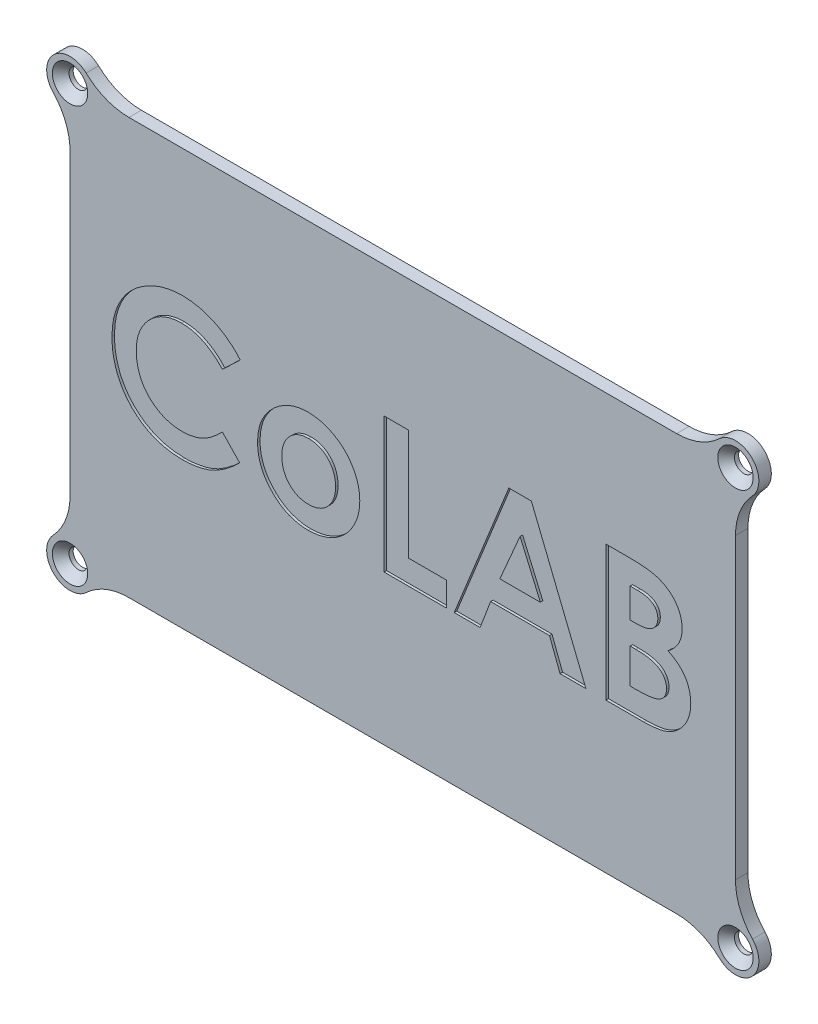
SolidWorks part; units mm, degrees
ref_plane "Front" through (0, 0, 0) normal (0, 0, 1) x (1, 0, 0)
ref_plane "Top" through (0, 0, 0) normal (0, 1, 0) x (1, 0, 0)
ref_plane "Right" through (0, 0, 0) normal (1, 0, 0) x (0, 0, -1)
sketch "Sketch2" plane through (0, 0, 0) normal (0, 0, 1) x (1, 0, 0)
  line L8 (80, -35.8441) -> (80, 35.8441)
  line L9 (65.8441, 50) -> (-65.8441, 50)
  line L10 (-80, 35.8441) -> (-80, -35.8441)
  line L11 (-65.8441, -50) -> (65.8441, -50)
  line L12 (80, -35.8441) -> (80, 35.8441)
  line L13 (65.8441, 50) -> (-65.8441, 50)
  line L14 (-80, 35.8441) -> (-80, -35.8441)
  line L15 (-65.8441, -50) -> (65.8441, -50)
  line L36 (76, -44) -> (76, 44)
  line L37 (-74, -46) -> (74, -46)
  line L38 (-76, 44) -> (-76, -44)
  line L39 (74, 46) -> (-74, 46)
  line L40 (76, -44) -> (76, 44)
  line L41 (-74, -46) -> (74, -46)
  line L42 (-76, 44) -> (-76, -44)
  line L43 (74, 46) -> (-74, 46)
  line L44 (73, 43) -> (-73, 43)
  line L45 (-73, 43) -> (-73, -43)
  line L46 (-73, -43) -> (73, -43)
  line L47 (73, -43) -> (73, 43)
  arc A12 (76.1393, -54.0909) -> (84.0909, -46.1393) centre (80, -50) ccw
  arc A13 (80, -35.8441) -> (84.0909, -46.1393) centre (95, -35.8441) ccw
  arc A14 (84.0909, 46.1393) -> (80, 35.8441) centre (95, 35.8441) ccw
  arc A15 (84.0909, 46.1393) -> (76.1393, 54.0909) centre (80, 50) ccw
  arc A16 (65.8441, 50) -> (76.1393, 54.0909) centre (65.8441, 65) ccw
  arc A17 (-76.1393, 54.0909) -> (-65.8441, 50) centre (-65.8441, 65) ccw
  arc A18 (-76.1393, 54.0909) -> (-84.0909, 46.1393) centre (-80, 50) ccw
  arc A19 (-80, 35.8441) -> (-84.0909, 46.1393) centre (-95, 35.8441) ccw
  arc A20 (-84.0909, -46.1393) -> (-80, -35.8441) centre (-95, -35.8441) ccw
  arc A21 (-84.0909, -46.1393) -> (-76.1393, -54.0909) centre (-80, -50) ccw
  arc A22 (-65.8441, -50) -> (-76.1393, -54.0909) centre (-65.8441, -65) ccw
  arc A23 (76.1393, -54.0909) -> (65.8441, -50) centre (65.8441, -65) ccw
  arc A24 (76.1393, -54.0909) -> (84.0909, -46.1393) centre (80, -50) ccw
  arc A25 (80, -35.8441) -> (84.0909, -46.1393) centre (95, -35.8441) ccw
  arc A26 (84.0909, 46.1393) -> (80, 35.8441) centre (95, 35.8441) ccw
  arc A27 (84.0909, 46.1393) -> (76.1393, 54.0909) centre (80, 50) ccw
  arc A28 (65.8441, 50) -> (76.1393, 54.0909) centre (65.8441, 65) ccw
  arc A29 (-76.1393, 54.0909) -> (-65.8441, 50) centre (-65.8441, 65) ccw
  arc A30 (-76.1393, 54.0909) -> (-84.0909, 46.1393) centre (-80, 50) ccw
  arc A31 (-80, 35.8441) -> (-84.0909, 46.1393) centre (-95, 35.8441) ccw
  arc A32 (-84.0909, -46.1393) -> (-80, -35.8441) centre (-95, -35.8441) ccw
  arc A33 (-84.0909, -46.1393) -> (-76.1393, -54.0909) centre (-80, -50) ccw
  arc A34 (-65.8441, -50) -> (-76.1393, -54.0909) centre (-65.8441, -65) ccw
  arc A35 (76.1393, -54.0909) -> (65.8441, -50) centre (65.8441, -65) ccw
  circle A40 centre (80, 50) radius 2.25
  circle A41 centre (-80, 50) radius 2.25
  circle A42 centre (-80, -50) radius 2.25
  circle A43 centre (80, -50) radius 2.25
  arc A44 (76, 44) -> (74, 46) centre (74, 44) ccw
  arc A45 (74, -46) -> (76, -44) centre (74, -44) ccw
  arc A46 (-76, -44) -> (-74, -46) centre (-74, -44) ccw
  arc A47 (-74, 46) -> (-76, 44) centre (-74, 44) ccw
  arc A48 (76, 44) -> (74, 46) centre (74, 44) ccw
  arc A49 (74, -46) -> (76, -44) centre (74, -44) ccw
  arc A50 (-76, -44) -> (-74, -46) centre (-74, -44) ccw
  arc A51 (-74, 46) -> (-76, 44) centre (-74, 44) ccw
  arc A56 (-73, 43) -> (-73, 43) centre (-73, 43) ccw
  arc A57 (-73, -43) -> (-73, -43) centre (-73, -43) ccw
  arc A58 (73, -43) -> (73, -43) centre (73, -43) ccw
  arc A59 (73, 43) -> (73, 43) centre (73, 43) ccw
  dimension "D3" = 4.5
  dimension "D1" = 0
  dimension "D2" = 1
  dimension "D4" = 3
extrude "Boss-Extrude1" add sketch "Sketch2" along normal blind 3 contours L43 A51 L42 A50 L41 A49 L40 A48 | A35 A24 A25 L12 A26 A27 A28 L13 A29 A30 A31 L14 A32 A33 A34 L15 A51 L43 A48 L40 A49 L41 A50 L42 A43 A42 A41 A40 | L46 L47 L44 L45 region at (79.1624, -42.1373, 0) region at (74.1579, -44.1579, 0) region at (0, 0, 0)
extrude "Boss-Extrude2" add sketch "Sketch2<3>" against normal blind 1 contours L43 A51 L42 A50 L41 A49 L40 A48 region at (74.1579, -44.1579, 0)
sketch "Sketch2<3>" plane through (0, 0, 0) normal (0, 0, 1) x (1, 0, 0) same geometry as "Sketch2"
sketch "Sketch3" plane through (0, 0, 0) normal (0, 0, -1) x (-1, 0, 0)
  line L0 (-6.5, 32.5) -> (-52.5, 32.5)
  line L1 (-4.5, -19.5) -> (-54.5, -19.5)
  line L2 (-4.5, -19.5) -> (-4.5, 34.5)
  line L3 (-4.5, 34.5) -> (-54.5, 34.5)
  line L4 (-54.5, -19.5) -> (-54.5, 34.5)
  line L5 (-52.5, -17.5) -> (-52.5, 32.5)
  line L6 (-6.5, -17.5) -> (-52.5, -17.5)
  line L7 (-6.5, -17.5) -> (-6.5, 32.5)
  circle A0 centre (-23.5, -11) radius 0.875
  circle A1 centre (-23.5, -11) radius 2.875
  circle A2 centre (-35.5, 26) radius 2.875
  circle A3 centre (-35.5, 26) radius 0.875
  dimension "D1" = 1.75
  dimension "D2" = 2
  dimension "D3" = 2
extrude "Boss-Extrude3" add sketch "Sketch3" along normal up to surface (2.9 mm away) contours A1 A0 | L4 L1 L2 L3 L7 L6 L5 L0 | A2 A3 region at (29.5, -18.7641, 0) region at (26.2937, -11, 0) region at (38.2937, 26, 0)
sketch "Sketch4" plane through (0, 0, 3) normal (0, 0, 1) x (1, 0, 0)
  line L0 (-72, -14) -> (80, -14) construction
  line L2 (80, -35.8441) -> (80, 35.8441) construction
  line L3 (-80, 35.8441) -> (-80, -35.8441) construction
  line L4 (-65.8441, -50) -> (65.8441, -50) construction
  text T0 "<b>CoLAB</b>" font "Century Gothic" height 32.5
  dimension "D1" = 8
  dimension "D2" = 36
extrude "Cut-Extrude1" cut sketch "Sketch4" against normal blind 0.6
chamfer "Chamfer1" distance 2 angle 45 4 edges at (82.25, 50, 3) (82.25, -50, 3) (-77.75, -50, 3) (-77.75, 50, 3)
